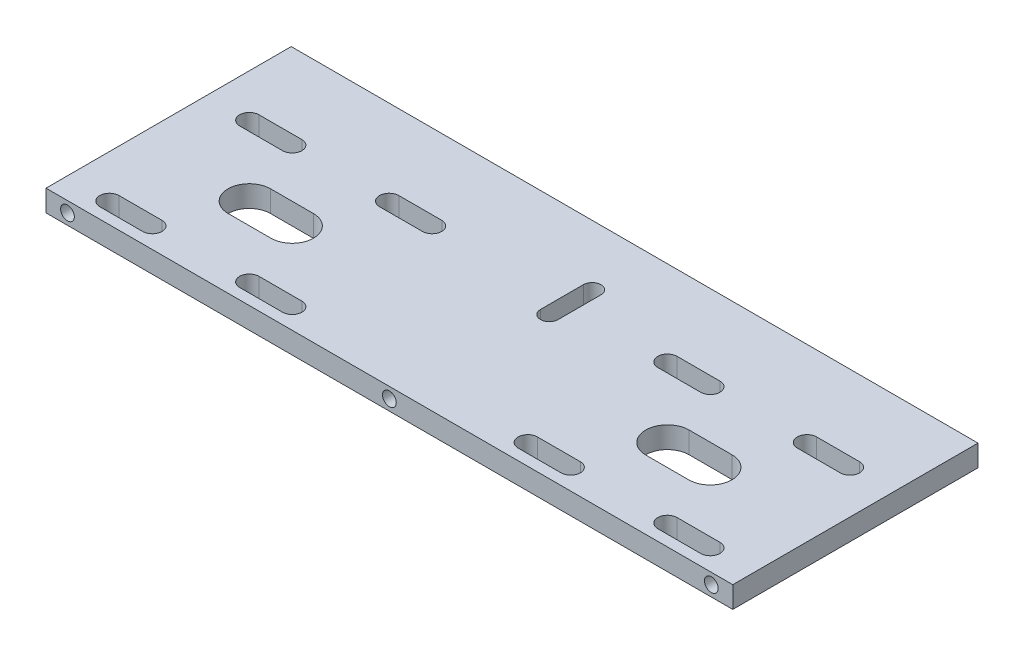
SolidWorks part; units mm, degrees
ref_plane "Front Plane" through (0, 0, 0) normal (0, 0, 1) x (1, 0, 0)
ref_plane "Top Plane" through (0, 0, 0) normal (0, 1, 0) x (1, 0, 0)
ref_plane "Right Plane" through (0, 0, 0) normal (1, 0, 0) x (0, 0, -1)
sketch "Sketch1" plane through (0, 0, 0) normal (0, 1, 0) x (1, 0, 0)
  line L0 (43.704, 0) -> (-43.704, 0) construction
  line L1 (-43.704, 0) -> (-43.704, 23) construction
  line L2 (-63.704, 20) -> (-23.704, 20) construction
  line L3 (-63.704, 20) -> (-63.704, -20) construction
  line L4 (-63.704, -20) -> (-23.704, -20) construction
  line L5 (-23.704, 20) -> (-23.704, -20) construction
  line L6 (-63.704, 20) -> (-23.704, -20) construction
  line L7 (-63.704, -20) -> (-23.704, 20) construction
  line L8 (-70, 16.296) -> (-60, 16.296) construction
  line L9 (-70, 18.546) -> (-60, 18.546)
  line L10 (-70, 14.046) -> (-60, 14.046)
  line L11 (-37.408, 16.296) -> (-27.408, 16.296) construction
  line L12 (-37.408, 18.546) -> (-27.408, 18.546)
  line L13 (-37.408, 14.046) -> (-27.408, 14.046)
  line L14 (-70, -16.296) -> (-60, -16.296) construction
  line L15 (-70, -18.546) -> (-60, -18.546)
  line L16 (-70, -14.046) -> (-60, -14.046)
  line L17 (-37.408, -16.296) -> (-27.408, -16.296) construction
  line L18 (-37.408, -18.546) -> (-27.408, -18.546)
  line L19 (-37.408, -14.046) -> (-27.408, -14.046)
  line L20 (-53.704, 0) -> (-43.704, 0) construction
  line L21 (-53.704, 4.9647) -> (-43.704, 4.9647)
  line L22 (-53.704, -4.9647) -> (-43.704, -4.9647)
  line L23 (37.4405, 16.2635) -> (27.4405, 16.2635) construction
  line L24 (22.704, -21) -> (64.704, -21) construction
  line L25 (22.704, -21) -> (22.704, 21) construction
  line L26 (22.704, 21) -> (64.704, 21) construction
  line L27 (64.704, -21) -> (64.704, 21) construction
  line L28 (22.704, -21) -> (64.704, 21) construction
  line L29 (22.704, 21) -> (64.704, -21) construction
  line L30 (37.4405, 14.0135) -> (27.4405, 14.0135)
  line L31 (37.4405, 18.5135) -> (27.4405, 18.5135)
  line L32 (69.9674, 16.2635) -> (59.9674, 16.2635) construction
  line L33 (69.9674, 14.0135) -> (59.9674, 14.0135)
  line L34 (69.9674, 18.5135) -> (59.9674, 18.5135)
  line L35 (53.704, 0) -> (43.704, 0) construction
  line L36 (53.704, -5.0502) -> (43.704, -5.0502)
  line L37 (53.704, 5.0502) -> (43.704, 5.0502)
  line L38 (37.4405, -16.2635) -> (27.4405, -16.2635) construction
  line L39 (37.4405, -14.0135) -> (27.4405, -14.0135)
  line L40 (37.4405, -18.5135) -> (27.4405, -18.5135)
  line L41 (69.9674, -16.2635) -> (59.9674, -16.2635) construction
  line L42 (69.9674, -14.0135) -> (59.9674, -14.0135)
  line L43 (69.9674, -18.5135) -> (59.9674, -18.5135)
  line L45 (-80, 21.0663) -> (80, 21.0663)
  line L46 (-80, 21.0663) -> (-80, -21.0663)
  line L47 (-80, -21.0663) -> (80, -21.0663)
  line L48 (80, 21.0663) -> (80, -21.0663)
  line L49 (-80, 21.0663) -> (80, -21.0663) construction
  line L50 (-80, -21.0663) -> (80, 21.0663) construction
  circle A0 centre (-43.704, 0) radius 23 construction
  circle A1 centre (-60, 16.296) radius 2.25 construction
  circle A2 centre (-27.408, 16.296) radius 2.25 construction
  circle A3 centre (-43.704, 0) radius 5 construction
  arc A4 (-70, 18.546) -> (-70, 14.046) centre (-70, 16.296) ccw
  arc A5 (-60, 14.046) -> (-60, 18.546) centre (-60, 16.296) ccw
  arc A6 (-37.408, 18.546) -> (-37.408, 14.046) centre (-37.408, 16.296) ccw
  arc A7 (-27.408, 14.046) -> (-27.408, 18.546) centre (-27.408, 16.296) ccw
  arc A8 (-70, -18.546) -> (-70, -14.046) centre (-70, -16.296) cw
  arc A9 (-60, -14.046) -> (-60, -18.546) centre (-60, -16.296) cw
  arc A10 (-37.408, -18.546) -> (-37.408, -14.046) centre (-37.408, -16.296) cw
  arc A11 (-27.408, -14.046) -> (-27.408, -18.546) centre (-27.408, -16.296) cw
  arc A12 (-53.704, 4.9647) -> (-53.704, -4.9647) centre (-53.704, 0) ccw
  arc A13 (-43.704, -4.9647) -> (-43.704, 4.9647) centre (-43.704, 0) ccw
  circle A14 centre (43.704, 0) radius 23 construction
  circle A15 centre (43.704, 0) radius 5 construction
  circle A16 centre (27.4405, 16.2635) radius 2.25 construction
  circle A17 centre (59.9674, 16.2635) radius 2.25 construction
  arc A18 (37.4405, 14.0135) -> (37.4405, 18.5135) centre (37.4405, 16.2635) ccw
  arc A19 (27.4405, 18.5135) -> (27.4405, 14.0135) centre (27.4405, 16.2635) ccw
  arc A20 (69.9674, 14.0135) -> (69.9674, 18.5135) centre (69.9674, 16.2635) ccw
  arc A21 (59.9674, 18.5135) -> (59.9674, 14.0135) centre (59.9674, 16.2635) ccw
  arc A22 (53.704, -5.0502) -> (53.704, 5.0502) centre (53.704, 0) ccw
  arc A23 (43.704, 5.0502) -> (43.704, -5.0502) centre (43.704, 0) ccw
  arc A24 (37.4405, -14.0135) -> (37.4405, -18.5135) centre (37.4405, -16.2635) cw
  arc A25 (27.4405, -18.5135) -> (27.4405, -14.0135) centre (27.4405, -16.2635) cw
  arc A26 (69.9674, -14.0135) -> (69.9674, -18.5135) centre (69.9674, -16.2635) cw
  arc A27 (59.9674, -18.5135) -> (59.9674, -14.0135) centre (59.9674, -16.2635) cw
  point P4 (0, 0)
  point P16 (-70, 16.296)
  point P18 (-65, 16.296)
  point P23 (-37.408, 16.296)
  point P25 (-32.408, 16.296)
  point P32 (-65, -16.296)
  point P39 (-32.408, -16.296)
  point P44 (-53.704, 0)
  point P46 (-48.704, 0)
  point P61 (37.4405, 16.2635)
  point P62 (69.9674, 16.2635)
  point P63 (53.704, 0)
  point P65 (32.4405, 16.2635)
  point P71 (64.9674, 16.2635)
  point P77 (48.704, 0)
  point P83 (32.4405, -16.2635)
  point P90 (64.9674, -16.2635)
  point P95 (0, 0)
  dimension "D4" = 10
  dimension "D5" = 2.25
  dimension "D7" = 2.25
  dimension "D12" = 10
  dimension "D15" = 2.25
  dimension "D16" = 2.25
  dimension "D19" = 10
  dimension "D1" = 87.408
  dimension "D2" = 40
  dimension "D3" = 40
  dimension "D6" = 10
  dimension "D8" = 10
  dimension "D9" = 10
  dimension "D10" = 42
  dimension "D11" = 42
  dimension "D13" = 10
  dimension "D14" = 10
  dimension "D17" = 23
  dimension "D18" = 23.0461
extrude "Boss-Extrude1" add sketch "Sketch1" along normal blind 5
sketch "Sketch4" plane through (0, 0, 21.0663) normal (0, 0, 1) x (1, 0, 0)
  line L0 (-80, 2.5) -> (80, 2.5) construction
  line L1 (-80, 5) -> (-80, 0) construction
  line L2 (80, 5) -> (80, 0) construction
  line L3 (0, 5) -> (0, 0) construction
  line L4 (-80, 5) -> (80, 5) construction
  circle A0 centre (-75, 2.5) radius 1.6
  circle A1 centre (75, 2.5) radius 1.6
  circle A2 centre (0, 2.5) radius 1.6
  dimension "D1" = 5
extrude "Cut-Extrude2" cut sketch "Sketch4" against normal blind 10
sketch "Sketch9" plane through (0, 0, 0) normal (0, -1, 0) x (1, 0, 0)
  line L0 (4.1205, -22.0663) -> (4.1205, -12.0663) construction
  line L1 (2.0705, -22.0663) -> (2.0705, -12.0663)
  line L2 (6.1705, -22.0663) -> (6.1705, -12.0663)
  line L3 (80, -21.0663) -> (-80, -21.0663) construction
  arc A0 (2.0705, -22.0663) -> (6.1705, -22.0663) centre (4.1205, -22.0663) ccw
  arc A1 (6.1705, -12.0663) -> (2.0705, -12.0663) centre (4.1205, -12.0663) ccw
  point P0 (9.8528, -14.3666)
  point P1 (4.1205, -17.0663)
  point P5 (4.1205, -17.0663)
  point P6 (4.1205, -17.0663)
  dimension "D2" = 2.05
  dimension "D3" = 10
  dimension "D4" = 4
extrude "Cut-Extrude4" cut sketch "Sketch9" against normal through all
sketch "Sketch10" plane through (0, 5, 0) normal (0, 1, 0) x (1, 0, 0)
  line L1 (-80, 21.0663) -> (80, 21.0663)
  line L2 (-80, 21.0663) -> (-80, 31.0663)
  line L3 (-80, 31.0663) -> (80, 31.0663)
  line L4 (80, 21.0663) -> (80, 31.0663)
  dimension "D1" = 10
  dimension "D2" = 160
extrude "Boss-Extrude4" add sketch "Sketch10" against normal up to surface (5 mm away) up to face at (32.4405, 0, 16.2635)
extrude "Cut-Extrude5" cut sketch "Sketch9<2>" against normal through all
sketch "Sketch9<2>" plane through (0, 0, 0) normal (0, -1, 0) x (1, 0, 0) same geometry as "Sketch9"
sketch "Sketch11" plane through (0, 5, 0) normal (0, 1, 0) x (1, 0, 0)
  line L1 (-80, 31.0663) -> (80, 31.0663)
  line L2 (-80, 31.0663) -> (-80, 36.0663)
  line L3 (-80, 36.0663) -> (80, 36.0663)
  line L4 (80, 31.0663) -> (80, 36.0663)
  dimension "D1" = 5
  dimension "D2" = 160
extrude "Boss-Extrude5" add sketch "Sketch11" against normal up to surface (5 mm away) up to face at (0, 0, -5)
equation "\"1p\"=10.266"
